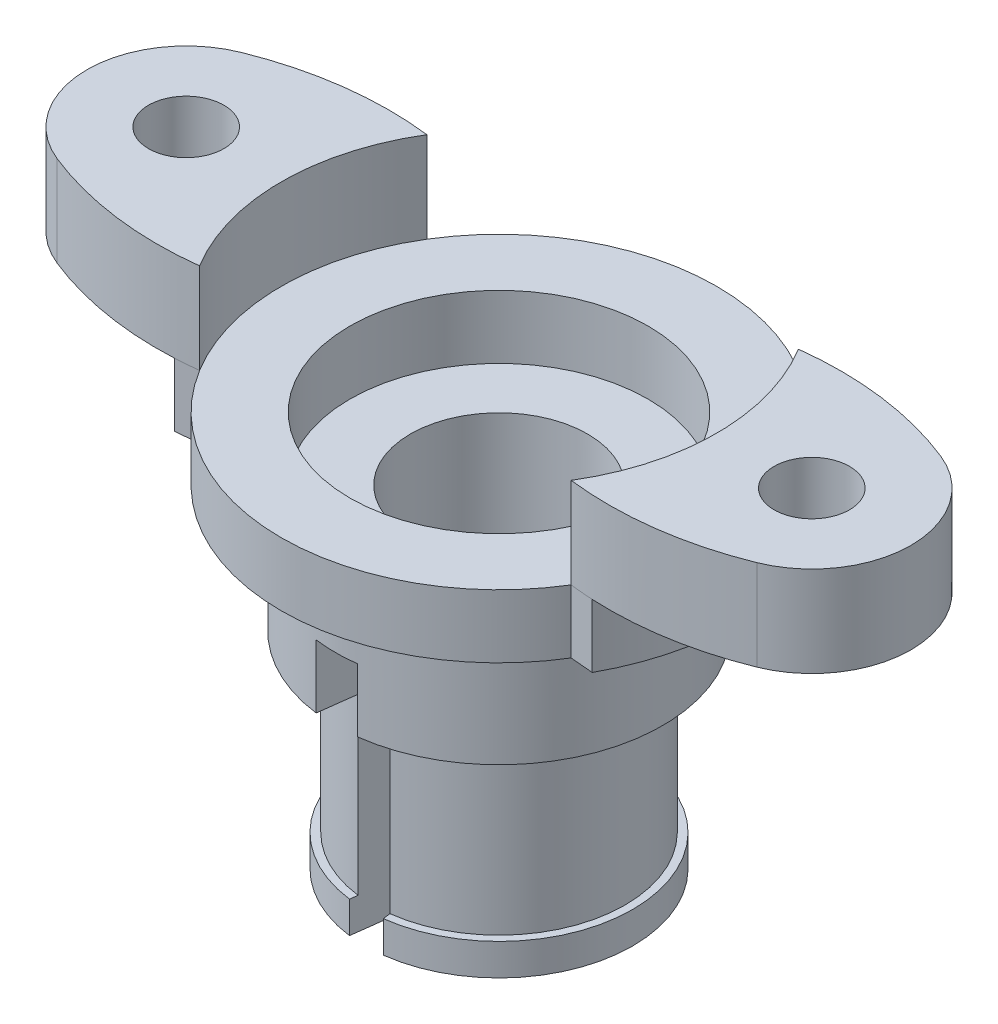
SolidWorks part; units mm, degrees
material "ABS"
ref_plane "Front Plane" through (0, 0, 0) normal (0, 0, 1) x (1, 0, 0)
ref_plane "Top Plane" through (0, 0, 0) normal (0, 1, 0) x (1, 0, 0)
ref_plane "Right Plane" through (0, 0, 0) normal (1, 0, 0) x (0, 0, -1)
sketch "Sketch1" plane through (0, 0, 0) normal (0, 1, 0) x (1, 0, 0)
  line L0 (0, -1044.2) -> (0, -22.1) construction
  line L3 (0, 23.55) -> (0, 1022.1) construction
  line L4 (0, 0) -> (17.0932, 0) construction
  line L5 (0, -14) -> (0, 14) construction
  circle A0 centre (0, 0) radius 14
  circle A1 centre (0, 0) radius 23.55
  dimension "D1" = 28
  dimension "D2" = 47.1
extrude "Boss-Extrude4" add sketch "Sketch1" along normal blind 10
sketch "Sketch6" plane through (0, 10, 0) normal (0, 1, 0) x (1, 0, 0)
  circle A0 centre (0, 0) radius 34.4
  circle A1 centre (0, 0) radius 23.55
  dimension "D1" = 47.1
  dimension "D2" = 68.8
extrude "Boss-Extrude5" add sketch "Sketch6" along normal blind 10 separate body
sketch "Sketch8" plane through (0, 20, 0) normal (0, 1, 0) x (1, 0, 0)
  line L0 (0, 0) -> (-65.0875, 0) construction
  line L1 (-49.4157, 0) -> (-55.2687, 14.5378) construction
  line L2 (0, 0) -> (0, 11.0429) construction
  circle A0 centre (-49.4157, 0) radius 5.9563
  arc A1 (-55.2687, 14.5378) -> (-55.2687, -14.5378) centre (-49.4157, 0) ccw
  arc A2 (-55.2687, 14.5378) -> (-29.3439, 17.9526) centre (-35.669, -34.1444) cw
  circle A3 centre (0, 0) radius 34.4 construction
  arc A4 (-55.2687, -14.5378) -> (-29.3439, -17.9526) centre (-35.669, 34.1444) ccw
  arc A5 (-29.3439, 17.9526) -> (-29.3439, -17.9526) centre (0, 0) ccw
  circle A6 centre (49.4157, 0) radius 5.9563
  arc A7 (55.2687, 14.5378) -> (29.3439, 17.9526) centre (35.669, -34.1444) ccw
  arc A8 (55.2687, 14.5378) -> (55.2687, -14.5378) centre (49.4157, 0) cw
  arc A9 (55.2687, -14.5378) -> (29.3439, -17.9526) centre (35.669, 34.1444) cw
  arc A10 (29.3439, 17.9526) -> (29.3439, -17.9526) centre (0, 0) cw
  dimension "D2" = 11.9126
  dimension "D1" = 65.0875
  dimension "D3" = 68.07
extrude "Boss-Extrude7" add sketch "Sketch8" along normal blind 14.3 separate body
sketch "Sketch9" plane through (0, 20, 0) normal (0, -1, 0) x (1, 0, 0)
  line L0 (-32.9943, 18.267) -> (-29.3439, 17.9526)
  line L1 (-32.9943, -18.267) -> (-29.3439, -17.9526)
  line L2 (0, 0) -> (0, 10.3797) construction
  line L3 (32.9943, 18.267) -> (29.3439, 17.9526)
  line L4 (32.9943, -18.267) -> (29.3439, -17.9526)
  arc A0 (-29.3439, 17.9526) -> (-29.3439, -17.9526) centre (0, 0) ccw
  arc A1 (-32.9943, 18.267) -> (-32.9943, -18.267) centre (0, 0) ccw
  arc A2 (-29.3439, 17.9526) -> (-55.2687, 14.5378) centre (-35.669, -34.1444) ccw construction
  arc A3 (-55.2687, -14.5378) -> (-29.3439, -17.9526) centre (-35.669, 34.1444) ccw construction
  arc A4 (29.3439, 17.9526) -> (29.3439, -17.9526) centre (0, 0) cw
  arc A5 (32.9943, 18.267) -> (32.9943, -18.267) centre (0, 0) cw
extrude "Boss-Extrude8" add sketch "Sketch9" along normal blind 10
sketch "Sketch10" plane through (0, 0, 0) normal (0, -1, 0) x (1, 0, 0)
  circle A0 centre (0, 0) radius 25.8324
  circle A1 centre (0, 0) radius 23.55
extrude "Boss-Extrude9" add sketch "Sketch10" against normal blind 10
sketch "Sketch11" plane through (0, 0, 0) normal (0, -1, 0) x (1, 0, 0)
  line L1 (-1.77, 13.8877) -> (-3.2659, 25.6251)
  line L2 (0, 0) -> (-10.6747, 0) construction
  line L3 (-1.77, -13.8877) -> (-3.2659, -25.6251)
  line L4 (1.77, -13.8877) -> (3.2659, -25.6251)
  line L5 (1.77, 13.8877) -> (3.2659, 25.6251)
  arc A0 (-1.77, 13.8877) -> (-1.77, -13.8877) centre (0, 0) ccw
  arc A1 (-3.2659, 25.6251) -> (-3.2659, -25.6251) centre (0, 0) ccw
  arc A2 (3.2659, -25.6251) -> (3.2659, 25.6251) centre (0, 0) ccw
  arc A3 (1.77, -13.8877) -> (1.77, 13.8877) centre (0, 0) ccw
  dimension "D1" = 14
extrude "Boss-Extrude10" add sketch "Sketch11" along normal blind 10
sketch "Sketch12" plane through (0, -10, 0) normal (0, -1, 0) x (1, 0, 0)
  line L0 (-1.77, 13.8877) -> (-2.518, 19.7564)
  line L1 (-1.77, 13.8877) -> (-3.2659, 25.6251) construction
  line L2 (1.77, 13.8877) -> (2.518, 19.7564)
  line L3 (3.2659, 25.6251) -> (1.77, 13.8877) construction
  line L4 (-1.77, 13.8877) -> (-1.6499, 12.9453)
  line L5 (-2.518, -19.7564) -> (-1.77, -13.8877)
  line L6 (-3.2659, -25.6251) -> (-1.77, -13.8877) construction
  line L7 (1.77, -13.8877) -> (2.518, -19.7564)
  line L8 (1.77, -13.8877) -> (3.2659, -25.6251) construction
  line L9 (-1.77, -13.8877) -> (-1.6499, -12.9453)
  line L10 (1.77, 13.8877) -> (1.6499, 12.9453)
  line L11 (1.77, -13.8877) -> (1.6499, -12.9453)
  arc A1 (-2.518, -19.7564) -> (-2.518, 19.7564) centre (0, 0) cw
  arc A2 (2.518, 19.7564) -> (2.518, -19.7564) centre (0, 0) cw
  arc A4 (-1.6499, 12.9453) -> (-1.6499, -12.9453) centre (0, 0) ccw
  arc A5 (1.6499, -12.9453) -> (1.6499, 12.9453) centre (0, 0) ccw
  dimension "D1" = 26.1
extrude "Boss-Extrude11" add sketch "Sketch12" along normal blind 27.5
sketch "Sketch13" plane through (0, -37.5, 0) normal (0, -1, 0) x (1, 0, 0)
  line L1 (0, 0) -> (-12.1608, 0) construction
  line L2 (0, 0) -> (0, 10.8173) construction
  line L10 (-1.6499, -12.9453) -> (-2.6702, -20.951)
  line L12 (1.6499, 12.9453) -> (2.6702, 20.951)
  line L13 (1.6499, -12.9453) -> (2.6702, -20.951)
  line L14 (-1.6499, 12.9453) -> (-2.6702, 20.951)
  arc A8 (-1.6499, 12.9453) -> (-1.6499, -12.9453) centre (0, 0) ccw
  arc A9 (2.6702, -20.951) -> (2.6702, 20.951) centre (0, 0) ccw
  arc A10 (1.6499, 12.9453) -> (1.6499, -12.9453) centre (0, 0) cw
  arc A11 (-2.6702, -20.951) -> (-2.6702, 20.951) centre (0, 0) cw
  point P1 (-2.9077, -22.8139)
  dimension "D1" = 13.05
fillet "Fillet4" radius 10 1 edges at (-13.05, -10, 0)
fillet "Fillet5" radius 10 1 edges at (13.05, -10, 0)
sketch "Sketch14" plane through (0, -37.5, 0) normal (0, -1, 0) x (1, 0, 0)
  line L0 (-1.6499, 12.9453) -> (-2.6702, 20.951)
  line L1 (0, 0) -> (0, 10.8173) construction
  line L2 (2.6702, -20.951) -> (1.6499, -12.9453)
  line L3 (-2.6702, -20.951) -> (-1.6499, -12.9453)
  line L4 (1.6499, 12.9453) -> (2.6702, 20.951)
  arc A0 (-2.6702, -20.951) -> (-2.6702, 20.951) centre (0, 0) cw
  arc A1 (-1.6499, -12.9453) -> (-1.6499, 12.9453) centre (0, 0) cw
  arc A2 (2.6702, -20.951) -> (2.6702, 20.951) centre (0, 0) ccw
  arc A3 (1.6499, -12.9453) -> (1.6499, 12.9453) centre (0, 0) ccw
extrude "Boss-Extrude13" add sketch "Sketch14" along normal blind 5
equation "\".5cmcm\"=1"
